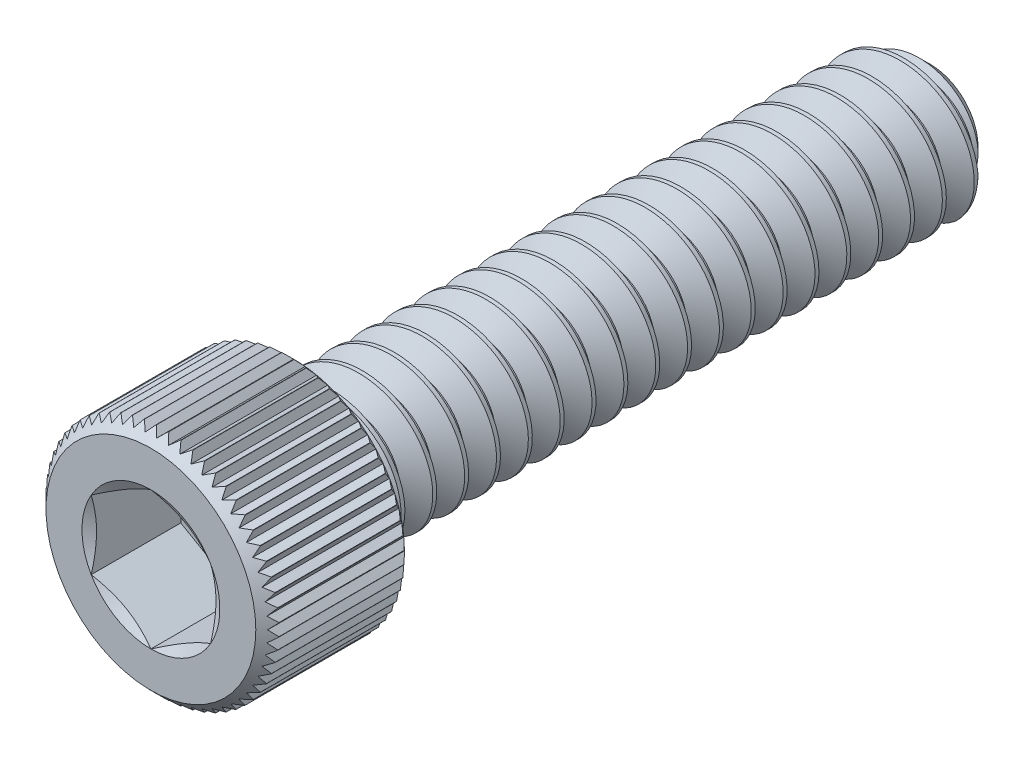
SolidWorks part; units mm, degrees
ref_plane "Front Plane" through (0, 0, 0) normal (0, 0, 1) x (1, 0, 0)
ref_plane "Top Plane" through (0, 0, 0) normal (0, 1, 0) x (1, 0, 0)
ref_plane "Right Plane" through (0, 0, 0) normal (1, 0, 0) x (0, 0, -1)
sketch "Sketch1" plane through (0, 0, 0) normal (1, 0, 0) x (0, 0, -1)
  line L0 (7.7724, 0) -> (-7.7724, 0) construction
  line L1 (-7.7724, 0) -> (-7.7724, 2.3241) construction
  line L2 (-4.9276, 1.4224) -> (-4.9276, 0) construction
  line L3 (7.1374, 0) -> (7.1374, 0.635) construction
  line L4 (-4.9276, 0) -> (-4.9276, -1.4224) construction
  point P6 (-7.7724, 1.1906)
  point P9 (-7.7724, -1.1906)
  point P10 (-4.9276, 0)
  point P13 (5.5499, -1.4224)
  dimension "Head Dia" = 4.6482
  dimension "Head Height" = 2.8448
  dimension "Thread OD" = 2.8448
  dimension "Pitch" = 0.635
  dimension "drive Size" = 2.3813
  dimension "D1" = 0.635
  dimension "D2" = 2.2225
sketch "Sketch2" plane through (0, 0, 0) normal (1, 0, 0) x (0, 0, -1)
  line L0 (7.7724, 0.9461) -> (7.2961, 1.4224)
  line L1 (-7.7724, 2.3241) -> (-4.9276, 2.3241)
  line L2 (-7.7724, 2.3241) -> (-7.7724, 0)
  line L4 (-4.9276, 2.3241) -> (-4.9276, 1.4224)
  line L5 (-4.9276, 1.4224) -> (7.2961, 1.4224)
  line L8 (7.7724, 0.9461) -> (7.7724, 0)
  line L9 (7.7724, 0) -> (-7.7724, 0) construction
  line L10 (7.7724, 0) -> (-7.7724, 0)
  dimension "D1" = 135
  dimension "D2" = 0.4763
revolve "Revolve1" add sketch "Sketch2" angle 360 about L10
sketch "Sketch4" plane through (0, 0, 7.7724) normal (0, 0, 1) x (1, 0, 0)
  line L1 (0, 1.3748) -> (-1.1906, 0.6874)
  line L2 (-1.1906, 0.6874) -> (-1.1906, -0.6874)
  line L3 (-1.1906, -0.6874) -> (0, -1.3748)
  line L4 (0, -1.3748) -> (1.1906, -0.6874)
  line L5 (1.1906, -0.6874) -> (1.1906, 0.6874)
  line L6 (1.1906, 0.6874) -> (0, 1.3748)
  circle A0 centre (0, 0) radius 1.1906 construction
  circle A1 centre (0, 0) radius 2.3241 construction
  circle A2 centre (0, 0) radius 2.3241 construction
  dimension "D1" = 2.3813
extrude "Cut-Extrude1" cut sketch "Sketch4" against normal blind 1.7859
sketch "Sketch5" plane through (0, 0, 7.7724) normal (0, 0, 1) x (1, 0, 0)
  circle A0 centre (0, 0) radius 1.3748
extrude "Cut-Extrude2" cut sketch "Sketch5" against normal blind 10 draft 60
chamfer "Chamfer1" distance 0.2324 angle 45 1 edges at (-2.3241, 0, 7.7724)
chamfer "Chamfer2" distance 0.1162 angle 45 1 edges at (-2.3241, 0, 4.9276)
sketch "Sketch3" plane through (0, 0, -7.7724) normal (0, 0, -1) x (-1, 0, 0)
  circle A0 centre (0, 0) radius 1.4224 construction
  circle A1 centre (0, 0) radius 1.4224
split "Split1" bodies to split 106 resulting bodies 114 115 split by face at (-2.2079, 0, 4.9276)
curve "Helix/Spiral1" pitch 0.635 height 13.335 radius 1.4224 centre (0, 0, -7.7724) axis (0, 0, 1) start towards (0, 1, 0)
sketch "Sketch7" plane through (0, 0, 0) normal (1, 0, 0) x (0, 0, -1)
  line L0 (7.7327, 1.4911) -> (8.0502, 0.9412) construction
  line L1 (8.0502, 0.9412) -> (8.3677, 1.4911) construction
  line L2 (8.3677, 1.4911) -> (7.7327, 1.4911) construction
  line L3 (7.7724, 1.4224) -> (8.328, 1.4224)
  line L4 (8.0502, 1.4911) -> (8.0502, 1.4224) construction
  line L5 (8.0502, 1.4224) -> (8.0502, 1.01) construction
  line L6 (8.0502, 1.01) -> (8.0502, 0.9412) construction
  line L7 (8.0105, 1.01) -> (8.0899, 1.01)
  line L8 (7.7526, 1.4568) -> (8.3479, 1.4568) construction
  line L9 (8.0899, 1.01) -> (8.328, 1.4224)
  line L10 (8.0105, 1.01) -> (7.7724, 1.4224)
  point P0 (8.0502, 1.4568)
  dimension "D1" = 0.635
  dimension "D2" = 0.0794
sweep "Cut-Sweep1" cut profiles "Sketch7" path "Helix/Spiral1" align with end faces yes
sketch "Sketch11" plane through (0, 0, 4.9276) normal (0, 0, -1) x (-1, 0, 0)
  circle A0 centre (0, 0) radius 1.4911
extrude "Boss-Extrude4" add sketch "Sketch11" along normal up to vertex (12.7 mm away) draft 45 up to point (0, 0, -7.7724)
sketch "Sketch9" plane through (0, 0, 4.9276) normal (0, 0, -1) x (-1, 0, 0)
  line L0 (0, 0) -> (0, 2.3241) construction
  line L1 (0, 2.2079) -> (-0.2436, 2.4403)
  line L2 (-0.2436, 2.4403) -> (0.2436, 2.4403)
  line L3 (0.2436, 2.4403) -> (0, 2.2079)
  line L4 (-0.1218, 2.3241) -> (0, 0) construction
  line L5 (0, 0) -> (0.1218, 2.3241) construction
  circle A0 centre (0, 0) radius 2.3241 construction
  circle A1 centre (0, 0) radius 2.2079 construction
  dimension "D1" = 0.2324
  dimension "D2" = 6
extrude "Cut-Extrude3" cut sketch "Sketch9" against normal up to next
pattern_circular "CirPattern1" count 60 over 360 about axis through (0, 0, 4.9276) along (0, 0, -1) of "Cut-Extrude3"
equation "\"D1@Sketch1\"=\"Pitch@Sketch1\""
equation "\"D2@Sketch2\"=\"D1@Sketch1\"*.75"
equation "\"D4@Helix/Spiral1\"=\"Pitch@Sketch1\""
equation "\"D3@Helix/Spiral1\"=\"Length@Sketch1\"+\"Pitch@Sketch1\""
equation "\"D1@Sketch4\"=\"drive Size@Sketch1\""
equation "\"D1@Cut-Extrude1\"=\"D1@Sketch4\"*.75"
equation "\"D19\"= \"D1@Sketch4\" * .75"
equation "\"D1@Chamfer1\" = \"Head Dia@Sketch1\" * .05"
equation "\"D1@Chamfer2\"=\"D1@Chamfer1\"/2"
equation "\"D2@Sketch7\"=\"D1@Sketch7\"/8"
equation "\"D1@Sketch7\"=\"D4@Helix/Spiral1\""
equation "\"D2@Sketch1\"=\"Pitch@Sketch1\"*3.5"
equation "\"D1@Sketch9\"=\"D1@Chamfer1\""
equation "\"D1@CirPattern1\"=\"D3@CirPattern1\"/\"D2@Sketch9\""
